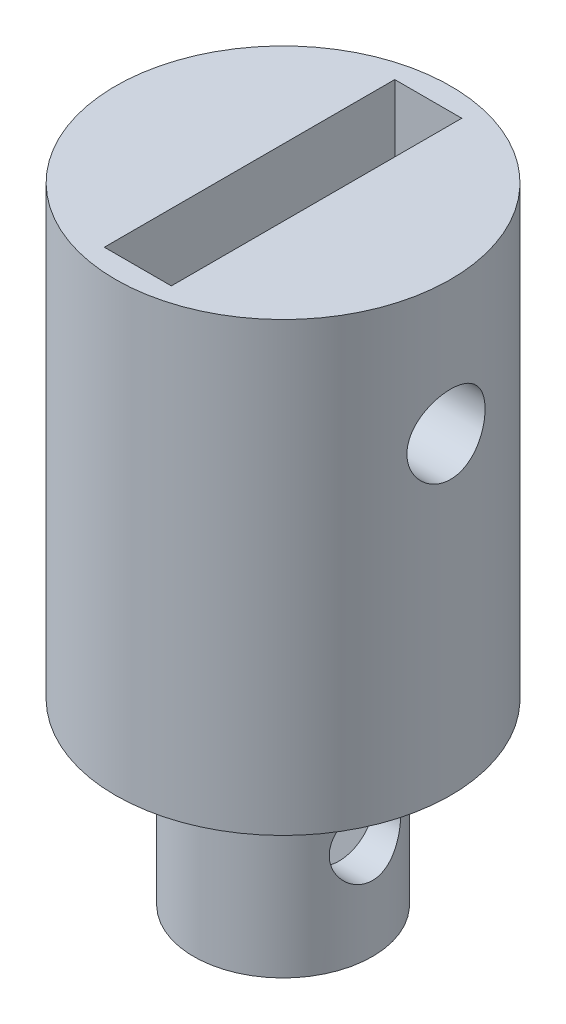
SolidWorks part; units mm, degrees
ref_plane "Front Plane" through (0, 0, 0) normal (0, 0, 1) x (1, 0, 0)
ref_plane "Top Plane" through (0, 0, 0) normal (0, 1, 0) x (1, 0, 0)
ref_plane "Right Plane" through (0, 0, 0) normal (1, 0, 0) x (0, 0, -1)
sketch "Sketch1" plane through (0, 0, 0) normal (0, 1, 0) x (1, 0, 0)
  circle A0 centre (0, 0) radius 7.5
  dimension "D1" = 15
extrude "Boss-Extrude1" add sketch "Sketch1" along normal blind 20
sketch "Sketch2" plane through (0, 20, 0) normal (0, 1, 0) x (1, 0, 0)
  line L1 (-1.5, 6.5) -> (1.5, 6.5)
  line L2 (-1.5, 6.5) -> (-1.5, -6.5)
  line L3 (-1.5, -6.5) -> (1.5, -6.5)
  line L4 (1.5, 6.5) -> (1.5, -6.5)
  point P7 (-1.5, 0)
  point P9 (0, 6.5)
  dimension "D1" = 3
  dimension "D2" = 13
extrude "Cut-Extrude1" cut sketch "Sketch2" against normal blind 10
ref_plane "Plane1" through (7.5, 0, 0) normal (1, 0, 0) x (0, 0, -1)
sketch "Sketch3" plane through (7.5, 0, 0) normal (1, 0, 0) x (0, 0, -1)
  line L0 (0, 20) -> (0, 0) construction
  line L1 (-6.5, 20) -> (6.5, 20) construction
  line L3 (7.5, 20) -> (-7.5, 20) construction
  circle A0 centre (0, 14) radius 1.75
  dimension "D1" = 3.5
  dimension "D2" = 6
extrude "Cut-Extrude2" cut sketch "Sketch3" against normal through all
sketch "Sketch4" plane through (0, 0, 0) normal (0, -1, 0) x (1, 0, 0)
  circle A0 centre (0, 0) radius 4
  dimension "D1" = 8
extrude "Boss-Extrude2" add sketch "Sketch4" along normal blind 8
sketch "Sketch5" plane through (0, -8, 0) normal (0, -1, 0) x (1, 0, 0)
  line L1 (2.5, -2.5) -> (-2.5, -2.5)
  line L2 (2.5, -2.5) -> (2.5, 2.5)
  line L3 (2.5, 2.5) -> (-2.5, 2.5)
  line L4 (-2.5, -2.5) -> (-2.5, 2.5)
  point P6 (0, -2.5)
  point P7 (2.5, 0)
  dimension "D1" = 5
  dimension "D2" = 5
extrude "Cut-Extrude3" cut sketch "Sketch5" against normal blind 6.2
sketch "Sketch6" plane through (7.5, 0, 0) normal (1, 0, 0) x (0, 0, -1)
  line L0 (2.5, -1.8) -> (-2.5, -1.8) construction
  circle A0 centre (0, -3.45) radius 1.6
  dimension "D1" = 3.2
  dimension "D2" = 1.65
extrude "Cut-Extrude4" cut sketch "Sketch6" against normal through all
